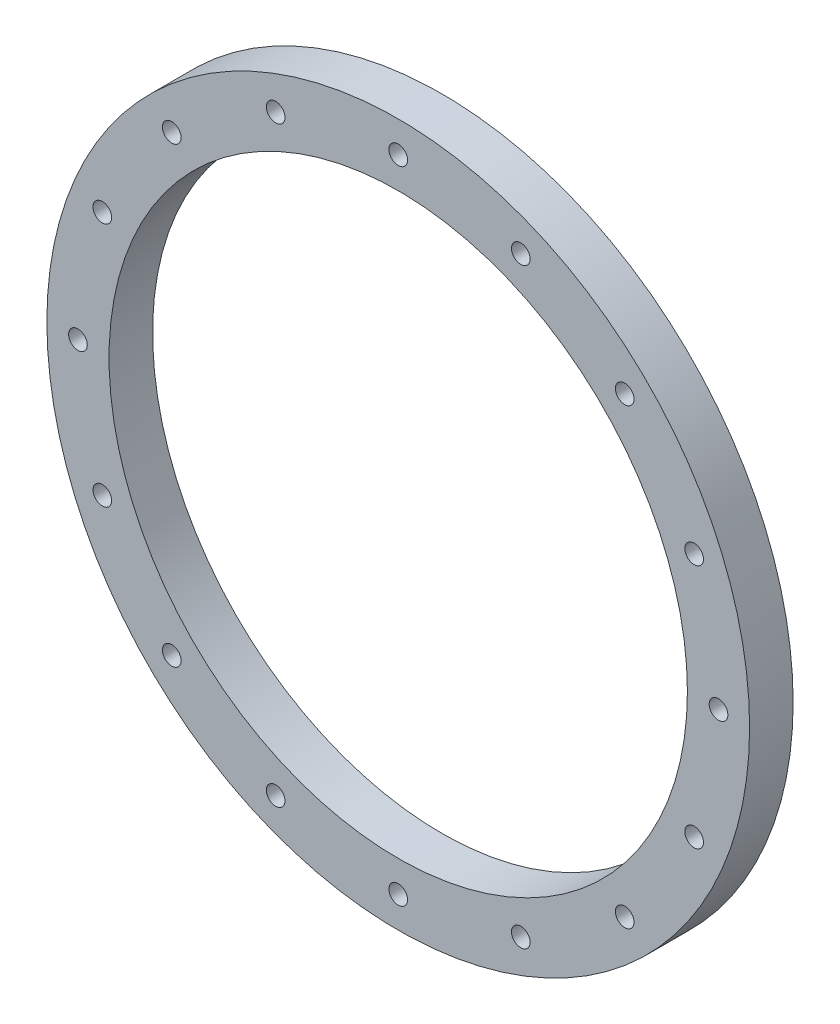
SolidWorks part; units mm, degrees
material "Stainless Steel 2205"
ref_plane "Front Plane" through (0, 0, 0) normal (0, 0, 1) x (1, 0, 0)
ref_plane "Top Plane" through (0, 0, 0) normal (0, 1, 0) x (1, 0, 0)
ref_plane "Right Plane" through (0, 0, 0) normal (1, 0, 0) x (0, 0, -1)
sketch "Sketch1" plane through (0, 0, 0) normal (0, 0, 1) x (1, 0, 0)
  circle A0 centre (0, 0) radius 464.965
  circle A1 centre (0, 0) radius 564.965
  dimension "D1" = 1129.93
  dimension "D2" = 100
extrude "Boss-Extrude1" add sketch "Sketch1" along normal blind 70
sketch "Sketch3" plane through (0, 0, 70) normal (0, 0, 1) x (1, 0, 0)
  line L0 (0, 0) -> (0, 514.965) construction
  line L1 (197.0686, 475.7656) -> (0, 0) construction
  circle A0 centre (0, 0) radius 514.965 construction
  circle A1 centre (0, 0) radius 564.965 construction
  circle A2 centre (197.0686, 475.7656) radius 15
  circle A3 centre (364.1352, 364.1352) radius 15
  circle A4 centre (475.7656, 197.0686) radius 15
  circle A5 centre (514.965, 0) radius 15
  circle A6 centre (475.7656, -197.0686) radius 15
  circle A7 centre (364.1352, -364.1352) radius 15
  circle A8 centre (197.0686, -475.7656) radius 15
  circle A9 centre (0, -514.965) radius 15
  circle A10 centre (-197.0686, -475.7656) radius 15
  circle A11 centre (-364.1352, -364.1352) radius 15
  circle A12 centre (-475.7656, -197.0686) radius 15
  circle A13 centre (-514.965, 0) radius 15
  circle A14 centre (-475.7656, 197.0686) radius 15
  circle A15 centre (-364.1352, 364.1352) radius 15
  circle A16 centre (-197.0686, 475.7656) radius 15
  circle A17 centre (0, 514.965) radius 15
  point P41 (0, 0)
  dimension "D1" = 50
  dimension "D2" = 30
  dimension "D3" = 22.5
  dimension "D4" = 16
extrude "Cut-Extrude2" cut sketch "Sketch3" against normal through all both and the other way through all
equation "\"hatchHoleDiameter\"= 600mm"
equation "\"hullThickness\"= 120mm"
equation "\"gasketHullInterconnectWidth\"= 100mm"
equation "\"collarThickness\"= 15"
equation "\"hatchTunnelLength\"=200"
equation "\"oRingDiameter\"=2"
equation "\"boltPatternRadiusInterconnect\"=500"
equation "\"interconnectBoltDiameter\"=30"
equation "\"hatchShaftDiameter\"=20"
equation "\"hatchMinima\"=50"
equation "\"hullDiameter\"=2000"
equation "\"hatchMaxima\"=180"
equation "\"bushingFlatHatch\"=15"
equation "\"hingePivotDiameter\"=20"
equation "\"handleWidth\"=250"
equation "\"handleHeight\"=160"
equation "\"handleThickness\"=25"
equation "\"FrameLength\"= 4300"
equation "\"FrameMidLength\"= 3000"
equation "\"TubeOD\"= 100"
equation "\"FrameBackFlat\"= 800"
equation "\"TubeWall\"=15"
equation "\"TopMemberAngle\"=120"
equation "\"FrameHight\"= 2500"
